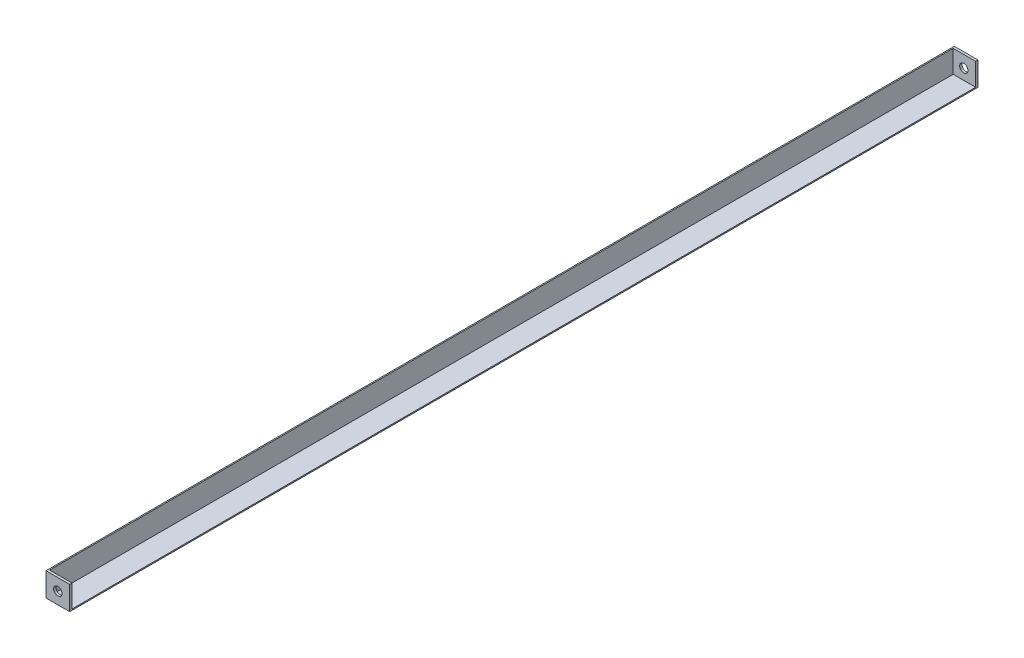
SolidWorks part; units mm, degrees
material "Galvanized Steel"
ref_plane "Front Plane" through (0, 0, 0) normal (0, 0, 1) x (1, 0, 0)
ref_plane "Top Plane" through (0, 0, 0) normal (0, 1, 0) x (1, 0, 0)
ref_plane "Right Plane" through (0, 0, 0) normal (1, 0, 0) x (0, 0, -1)
sketch "Sketch1" plane through (0, 0, 0) normal (0, 0, 1) x (1, 0, 0)
  line L0 (31.75, 1.5875) -> (1.5875, 1.5875)
  line L1 (0, 0) -> (31.75, 0)
  line L2 (0, 0) -> (0, 31.75)
  line L3 (0, 31.75) -> (1.5875, 31.75)
  line L4 (31.75, 0) -> (31.75, 1.5875)
  line L5 (1.5875, 1.5875) -> (1.5875, 31.75)
  dimension "D1" = 31.75
  dimension "D2" = 1.5875
extrude "Boss-Extrude1" add sketch "Sketch1" along normal mid plane 1219.2
sketch "Sketch2" plane through (0, 0, 0) normal (0, 0, 1) x (1, 0, 0)
  line L0 (31.75, 0) -> (31.75, 1.5875) construction
  line L1 (0, 0) -> (31.75, 0)
  line L2 (0, 0) -> (0, 31.75)
  line L3 (0, 31.75) -> (31.75, 31.75)
  line L4 (31.75, 0) -> (31.75, 31.75)
  circle A0 centre (15.875, 15.875) radius 5.588
  point P9 (15.875, 0)
  point P10 (0, 15.875)
  dimension "D1" = 11.176
extrude "Boss-Extrude2" add sketch "Sketch2" against normal blind 3.175 from offset 609.6
mirror "Mirror1" about plane through (0, 0, 0) normal (0, 0, 1) of "Boss-Extrude2"
